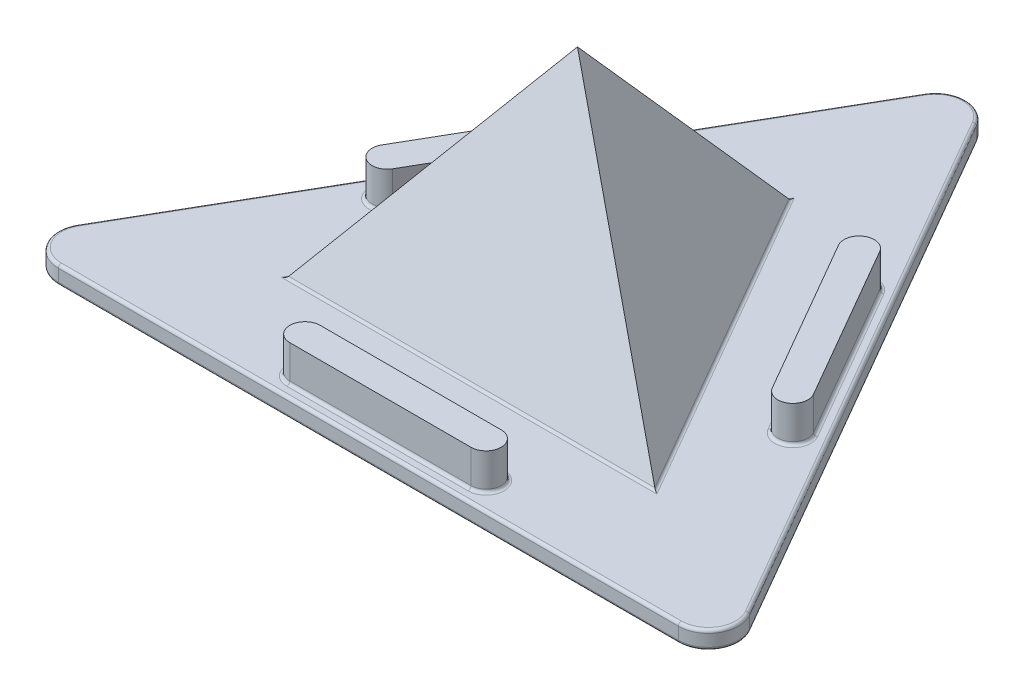
SolidWorks part; units mm, degrees
ref_plane "Front Plane" through (0, 0, 0) normal (0, 0, 1) x (1, 0, 0)
ref_plane "Top Plane" through (0, 0, 0) normal (0, 1, 0) x (1, 0, 0)
ref_plane "Right Plane" through (0, 0, 0) normal (1, 0, 0) x (0, 0, -1)
sketch "Sketch4" plane through (0, 0, 0) normal (0, 1, 0) x (1, 0, 0)
  line L5 (-60, -52.32) -> (60, -52.32)
  line L6 (60, -52.32) -> (0, 51.6)
  line L7 (-60, -52.32) -> (0, 51.6)
  dimension "D1" = 119.9974
  dimension "D2" = 60
  dimension "D3" = 51.6
extrude "Boss-Extrude2" add sketch "Sketch4" against normal blind 3
fillet "Fillet2" radius 5 3 edges at (0, -1.5, -51.6) (-60, -1.5, 52.32) (60, -1.5, 52.32)
sketch "Sketch6" plane through (0, 0, 0) normal (0, 1, 0) x (1, 0, 0)
  line L0 (0, -52.32) -> (0, -47.82)
  line L1 (-51.3396, -52.32) -> (51.3396, -52.32) construction
  line L2 (-15, -47.82) -> (15, -47.82) construction
  line L3 (29.9999, -0.3598) -> (26.1028, -2.6099)
  line L4 (-15, -45.32) -> (15, -45.32)
  line L5 (-15, -50.32) -> (15, -50.32)
  line L6 (55.6697, -44.8199) -> (4.3301, 44.1003) construction
  line L7 (18.6027, 10.3804) -> (33.603, -15.6002) construction
  line L8 (-29.9999, -0.3598) -> (-26.1028, -2.6099)
  line L9 (20.7677, 11.6304) -> (35.768, -14.3501)
  line L10 (16.4376, 9.1304) -> (31.4379, -16.8502)
  line L12 (-4.3301, 44.1003) -> (-55.6697, -44.8199) construction
  line L13 (-18.6027, 10.3804) -> (-33.603, -15.6002) construction
  line L15 (-16.4376, 9.1304) -> (-31.4379, -16.8502)
  line L16 (-20.7677, 11.6304) -> (-35.768, -14.3501)
  arc A0 (-15, -45.32) -> (-15, -50.32) centre (-15, -47.82) ccw
  arc A1 (15, -50.32) -> (15, -45.32) centre (15, -47.82) ccw
  arc A2 (20.7677, 11.6304) -> (16.4376, 9.1304) centre (18.6027, 10.3804) ccw
  arc A3 (31.4379, -16.8502) -> (35.768, -14.3501) centre (33.603, -15.6002) ccw
  arc A4 (-16.4376, 9.1304) -> (-20.7677, 11.6304) centre (-18.6027, 10.3804) ccw
  arc A5 (-35.768, -14.3501) -> (-31.4379, -16.8502) centre (-33.603, -15.6002) ccw
  point P9 (0, -47.82)
  point P20 (26.1028, -2.6099)
  point P31 (-26.1028, -2.6099)
  dimension "D1" = 2.5
  dimension "D2" = 19.9017
  dimension "D3" = 24.2318
  dimension "D4" = 29.5669
extrude "Boss-Extrude3" add sketch "Sketch6" along normal blind 6 contours L16 A5 L15 A4 | L10 A3 L9 A2 | L5 A1 L4 A0 region at (0, 0, 45.6736) region at (24.1984, 0, -4.9509) region at (-24.2571, 0, 3.6755)
sketch "Sketch7" plane through (0, 0, 0) normal (0, 1, 0) x (1, 0, 0)
  line L0 (30.5547, -35.32) -> (0, 17.6007)
  line L1 (0, 17.6007) -> (-30.5547, -35.32)
  line L2 (-30.5547, -35.32) -> (30.5547, -35.32)
  line L3 (-60, -52.32) -> (60, -52.32)
  line L4 (60, -52.32) -> (0, 51.6)
  line L5 (0, 51.6) -> (-60, -52.32)
  line L6 (-60, -52.32) -> (60, -52.32)
  line L7 (60, -52.32) -> (0, 51.6)
  line L8 (0, 51.6) -> (-60, -52.32)
  dimension "D1" = 0
  dimension "D2" = 17
extrude "Boss-Extrude4" add sketch "Sketch7" along normal blind 40 draft 24 contours L0 L1 L2
shell "Shell1" thickness 2 removed face at (0, -3, 17.6799)
fillet "Fillet3" radius 0.5 33 edges at (28.2679, -3, 1.3599) (53.9377, -3, 48.82) (0, -3, 50.32) (-53.9377, -3, 48.82) (-28.2679, -3, 1.3599) (0, -3, -44.6002) (-55.6698, -3, 49.82) (0, -3, 52.32) (55.6698, -3, 49.82) (29.9999, -3, 0.3598) (0, -3, -46.6002) (-29.9999, -3, 0.3598) (-15.2774, 0, 8.8596) (0, 0, 35.32) (15.2774, 0, 8.8596) (55.6698, 0, 49.82) (0, 0, 52.32) (-55.6698, 0, 49.82) (-29.9999, 0, 0.3598) (0, 0, -46.6002) (29.9999, 0, 0.3598) (-23.9378, 0, 3.8599) (-17.3526, 0, -12.5454) (-28.2679, 0, 1.3599) (-34.853, 0, 17.7652) (28.2679, 0, 1.3599) (17.3526, 0, -12.5454) (23.9378, 0, 3.8599) (34.853, 0, 17.7652) (0, 0, 45.32) (-17.5, 0, 47.82) (0, 0, 50.32) (17.5, 0, 47.82)
